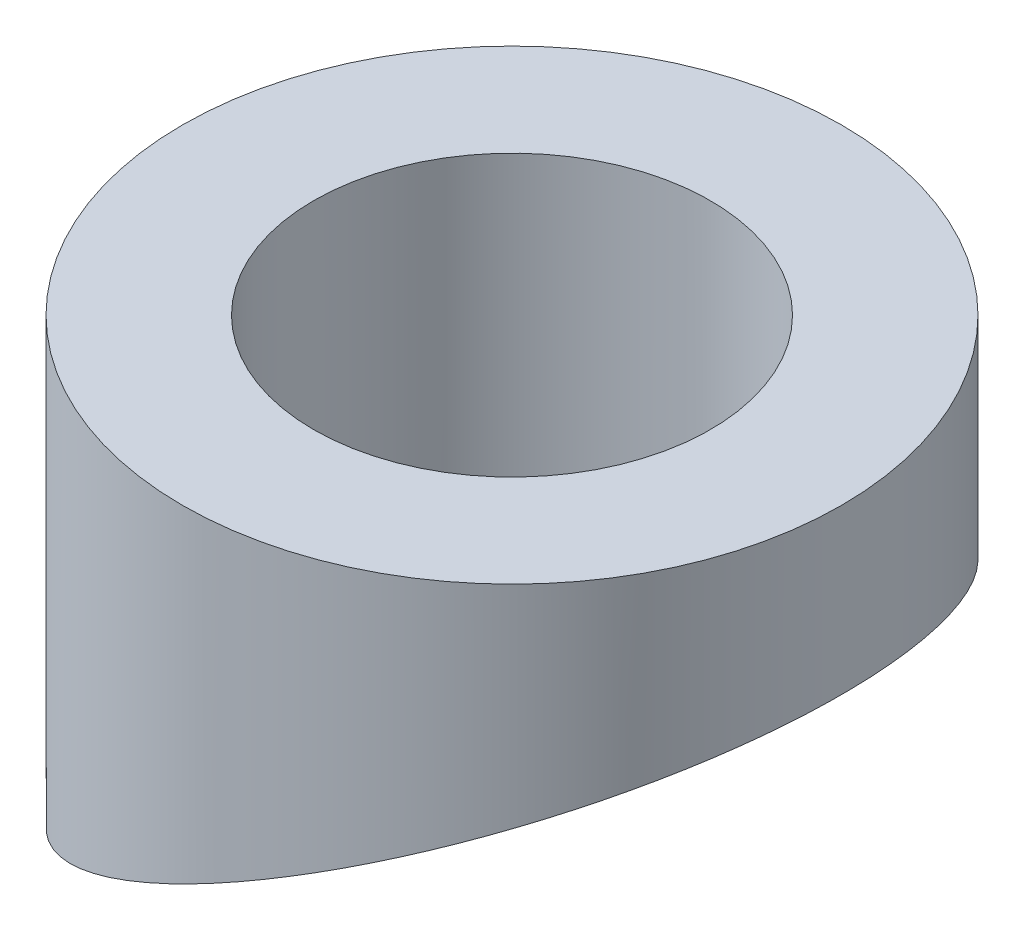
SolidWorks part; units mm, degrees
ref_plane "Front Plane" through (0, 0, 0) normal (0, 0, 1) x (1, 0, 0)
ref_plane "Top Plane" through (0, 0, 0) normal (0, 1, 0) x (1, 0, 0)
ref_plane "Right Plane" through (0, 0, 0) normal (1, 0, 0) x (0, 0, -1)
sketch "Sketch1" plane through (0, 0, 0) normal (0, 1, 0) x (1, 0, 0)
  circle A0 centre (0, 0) radius 6.05
  circle A1 centre (0, 0) radius 10.05
  dimension "D1" = 12.1
  dimension "D2" = 4
extrude "Boss-Extrude1" add sketch "Sketch1" along normal blind 15
sketch "Sketch3" plane through (0, 0, 0) normal (0, 0, 1) x (1, 0, 0)
  line L0 (-10.05, 0) -> (10.05, 10)
  line L1 (10.05, 0) -> (10.05, 15) construction
  line L2 (10.05, 10) -> (10.05, 0)
  line L3 (10.05, 0) -> (-10.05, 0)
  dimension "D1" = 10
extrude "Cut-Extrude1" cut sketch "Sketch3" against normal mid plane 30
